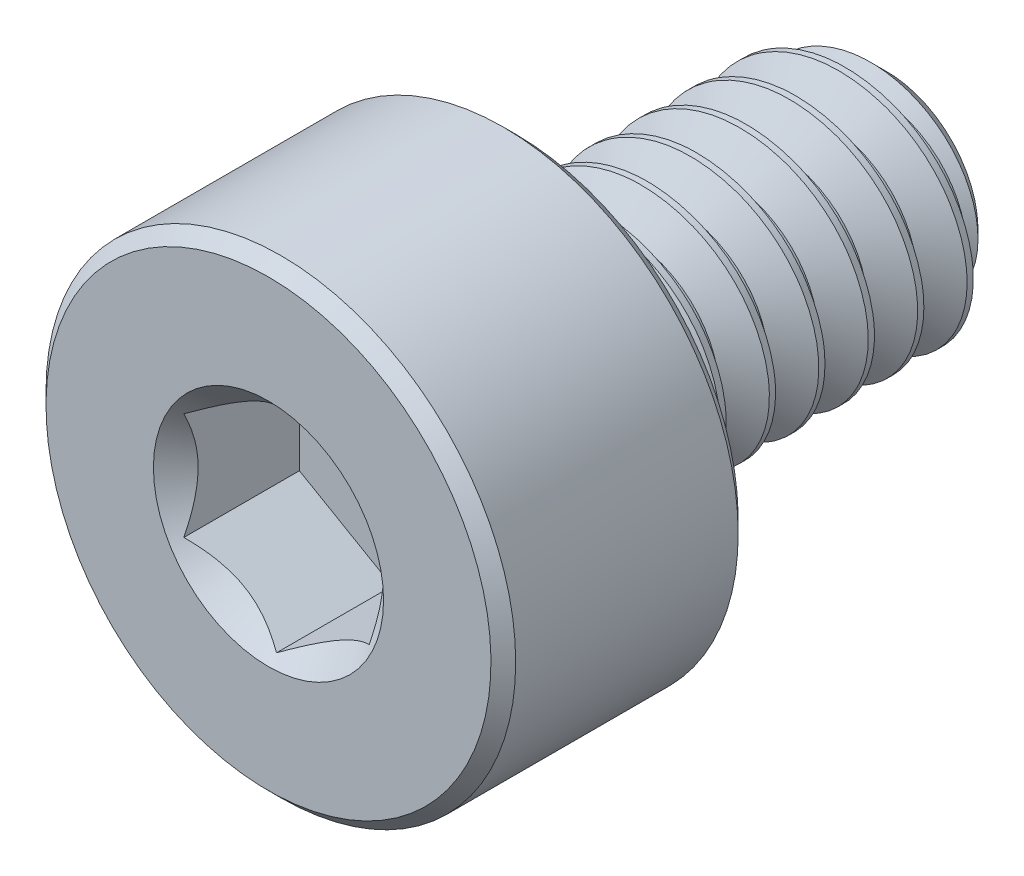
SolidWorks part; units mm, degrees
ref_plane "Front Plane" through (0, 0, 0) normal (0, 0, 1) x (1, 0, 0)
ref_plane "Top Plane" through (0, 0, 0) normal (0, 1, 0) x (1, 0, 0)
ref_plane "Right Plane" through (0, 0, 0) normal (1, 0, 0) x (0, 0, -1)
sketch "Sketch1" plane through (0, 0, 0) normal (1, 0, 0) x (0, 0, -1)
  line L0 (-2.5, 0) -> (2.5, 0) construction
  line L1 (2.5, 0) -> (2.5, 0.7402) construction
  line L2 (2.5, 0.7402) -> (2.2402, 1) construction
  line L3 (2.2402, 1) -> (2.2, 1) construction
  line L4 (2.2, 1) -> (-0.5, 1) construction
  line L5 (-0.5, 1) -> (-0.5, 1.9) construction
  line L6 (-0.5, 1.9) -> (-2.5, 1.9) construction
  line L7 (-2.5, 1.9) -> (-2.5, 0) construction
  line L8 (2.5, 0.7402) -> (2.5, 1) construction
  line L9 (2.475, 1.0433) -> (2.675, 0.6969) construction
  line L10 (2.675, 0.6969) -> (2.875, 1.0433) construction
  line L11 (2.875, 1.0433) -> (2.475, 1.0433) construction
  line L12 (2.675, 1.0433) -> (2.675, 1) construction
  line L13 (2.675, 0.6969) -> (2.675, 0.7402) construction
  line L14 (2.65, 0.7402) -> (2.7, 0.7402) construction
  line L15 (2.5, 1) -> (2.85, 1) construction
  line L16 (2.4875, 1.0217) -> (2.8625, 1.0217) construction
  line L17 (2.5, 0) -> (2.5, -1) construction
  line L18 (-0.6, 1.9) -> (-0.5, 1.8) construction
  line L19 (-2.4, 1.9) -> (-2.5, 1.8) construction
  line L20 (-0.5, 1) -> (-0.5, 0) construction
  line L21 (-0.5, 0.5) -> (0.5, 0.5) construction
  line L22 (0.5, 0.5) -> (1.5, 0.5) construction
  line L23 (1.5, 0.5) -> (2.5, 0.5) construction
  line L24 (0.5, 0.5) -> (0.5, 1) construction
  line L25 (0.5, 1) -> (0.5, 1.9) construction
  line L26 (1.5, 0.5) -> (1.5, 1.9) construction
  point P0 (-2.5, 0.75)
  point P3 (1.5, 1)
  point P4 (0, 0)
  point P18 (1.5, 1)
  point P22 (2.675, 0.7402)
  point P24 (2.2, 1)
  point P25 (2.675, 1)
  point P28 (2.675, 1.0217)
  point P29 (1.5, -1)
  point P30 (0.5, 1)
  point P31 (-1.5, 1.9)
  point P37 (-0.85, 1.9)
  point P38 (-2.35, 1.9)
  point P45 (0.5, 0.5)
  point P46 (1.5, 0.5)
  dimension "D2" = 0.05
  dimension "D7" = 0.1
  dimension "D8" = 0.1
  dimension "D9" = 0.1
  dimension "D10" = 0.05
  dimension "D11" = 0.25
  dimension "Drive Size" = 1.5
  dimension "Head Diameter" = 3.8
  dimension "Head Height" = 2
  dimension "Thread Pitch" = 0.4
  dimension "Thread Size" = 2
  dimension "Length" = 3
  dimension "D12" = 0.3
  dimension "D4" = 1
  dimension "D3" = 45
sketch "Sketch2" plane through (0, 0, 0) normal (1, 0, 0) x (0, 0, -1)
  line L0 (-2.5, 0) -> (-2.5, 1.8)
  line L1 (-2.4, 1.9) -> (-0.6, 1.9)
  line L2 (-0.5, 1.8) -> (-0.5, 1.1)
  line L4 (2.2402, 1) -> (2.5, 0.7402)
  line L5 (2.5, 0.7402) -> (2.5, 0)
  line L6 (-0.5, 1.9) -> (-2.5, 1.9) construction
  line L7 (2.5, 0) -> (-2.5, 0)
  line L8 (-2.4, 1.9) -> (-2.5, 1.8) construction
  line L10 (-2.4, 1.9) -> (-2.5, 1.8)
  line L14 (-0.6, 1.9) -> (-0.5, 1.8) construction
  line L16 (-0.6, 1.9) -> (-0.5, 1.8)
  line L17 (-0.5, 1) -> (-0.5, 1.9) construction
  line L19 (-0.4, 1) -> (2.2402, 1)
  line L20 (2.2, 1) -> (-0.5, 1) construction
  arc A1 (-0.5, 1.1) -> (-0.4, 1) centre (-0.4, 1.1) ccw
  dimension "D3" = 0.1
revolve "Revolve1" add sketch "Sketch2" angle 360 about L7
sketch "Sketch3" plane through (0, 0, 2.5) normal (0, 0, 1) x (1, 0, 0)
  line L1 (0.75, -0.433) -> (0.75, 0.433)
  line L2 (0.75, 0.433) -> (0, 0.866)
  line L3 (0, 0.866) -> (-0.75, 0.433)
  line L4 (-0.75, 0.433) -> (-0.75, -0.433)
  line L5 (-0.75, -0.433) -> (0, -0.866)
  line L6 (0, -0.866) -> (0.75, -0.433)
  circle A0 centre (0, 0) radius 0.75 construction
  circle A1 centre (0, 0) radius 1.9 construction
  circle A2 centre (0, 0) radius 1.9 construction
  circle A3 centre (0, 0) radius 0.866 construction
  point P13 (0, 0)
  dimension "D1" = 1.7321
extrude "Cut-Extrude1" cut sketch "Sketch3" against normal offset from surface (1 mm away) 1 up to face at (0, 1.8, 0.5)
sketch "Sketch4" plane through (0, 0, 2.5) normal (0, 0, 1) x (1, 0, 0)
  circle A0 centre (0, 0) radius 0.931
  dimension "D1" = 1.862
extrude "Cut-Extrude2" cut sketch "Sketch4" against normal up to vertex (1 mm away) draft 45 up to point (0, 1.9, 1.5)
sketch "Sketch11" plane through (0, 0, 0) normal (1, 0, 0) x (0, 0, -1)
  line L0 (-2.5, 0) -> (2.5, 0) construction
  line L1 (-2.5, 0) -> (2.5, 0) construction
  line L2 (0.0625, 0) -> (0.0625, 1) construction
  line L3 (2.2, 1) -> (-0.5, 1) construction
  line L4 (1.9375, 0) -> (1.9375, 1) construction
  line L6 (2.5, 0.7402) -> (2.5, 1) construction
  point P2 (0.0625, 0)
  point P3 (1.9375, 0)
  dimension "D1" = 0.5625
  dimension "D2" = 0.5625
sketch "Sketch6" plane through (0, 0, -2.5) normal (0, 0, -1) x (-1, 0, 0)
  circle A0 centre (0, 0) radius 1
curve "Helix/Spiral1" pitch 0.4 height 3.4 turns 8.5
sketch "Sketch10" plane through (0, 0, 0) normal (1, 0, 0) x (0, 0, -1)
  line L0 (-0.4, -1.9) -> (-0.4, 1.9)
  line L5 (-2.5, 0) -> (2.5, 0) construction
  line L6 (-0.4, 1) -> (-0.4, -1) construction
  point P3 (-0.4, 0)
split "Split1" trim tools "Sketch10" bodies to split 106 resulting bodies 114 115
sketch "Sketch7" plane through (0, 0, 0) normal (1, 0, 0) x (0, 0, -1)
  line L0 (2.4875, 1.0217) -> (2.8625, 1.0217)
  line L1 (2.8625, 1.0217) -> (2.7, 0.7402)
  line L2 (2.7, 0.7402) -> (2.65, 0.7402)
  line L3 (2.65, 0.7402) -> (2.4875, 1.0217)
sweep "Cut-Sweep1" cut profiles "Sketch7" path "Helix/Spiral1" align with end faces yes
sketch "Sketch8" plane through (0, 0, 0) normal (1, 0, 0) x (0, 0, -1)
  line L0 (-0.5, 0) -> (-0.5, 1)
  line L1 (-0.4, -1) -> (-0.4, 1) construction
  line L2 (-0.5, 1) -> (-0.4, 1)
  line L4 (-0.4, 1) -> (0.1774, 0)
  line L5 (0.1774, 0) -> (-0.5, 0)
  line L6 (2.2, 1) -> (-0.5, 1) construction
  line L7 (-2.5, 0) -> (2.5, 0) construction
  dimension "D1" = 60
revolve "Revolve2" add sketch "Sketch8" angle 360 about L5
equation "\"D2@Sketch1\" = \"Thread Pitch@Sketch1\" / 8"
equation "\"D4@Helix/Spiral1\" = \"Thread Pitch@Sketch1\""
equation "\"D7@Sketch1\" = \"Head Height@Sketch1\" * .05"
equation "\"D8@Sketch1\"=\"D7@Sketch1\""
equation "\"D9@Sketch1\"=\"D7@Sketch1\""
equation "\"D10@Sketch1\"=\"D7@Sketch1\"/2"
equation "\"D11@Sketch1\"=\"D10@Sketch1\"*5"
equation "\"D4@Sketch1\"=\"Thread Pitch@Sketch1\"*2.5"
equation "\"D12@Sketch1\"=\"Thread Pitch@Sketch1\"*.75"
equation "\"D3@Helix/Spiral1\"=\"Length@Sketch1\"+\"Thread Pitch@Sketch1\""
equation "\"D3@Sketch2\"=\"Thread Size@Sketch1\"*0.05"
equation "\"D1@Sketch11\"=\"Length@Sketch1\"*0.1875"
equation "\"D2@Sketch11\"=\"D1@Sketch11\""
equation "\"D1@Sketch4\"=\"D1@Sketch3\"*1.075"
